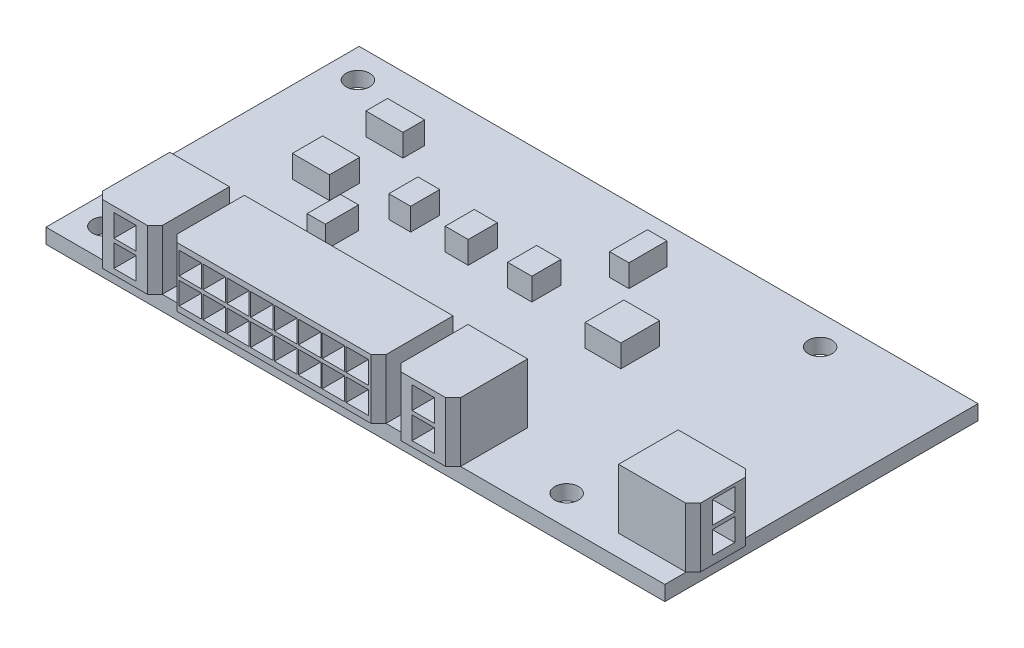
SolidWorks part; units mm, degrees
ref_plane "Front" through (0, 0, 0) normal (0, 0, 1) x (1, 0, 0)
ref_plane "Top" through (0, 0, 0) normal (0, 1, 0) x (1, 0, 0)
ref_plane "Right" through (0, 0, 0) normal (1, 0, 0) x (0, 0, -1)
sketch "Sketch1" plane through (0, 0, 0) normal (0, 1, 0) x (1, 0, 0)
  line L1 (0, 0) -> (83, 0)
  line L2 (0, 0) -> (0, 42)
  line L3 (0, 42) -> (83, 42)
  line L4 (83, 0) -> (83, 42)
  dimension "D1" = 42
  dimension "D2" = 83
extrude "Boss-Extrude1" add sketch "Sketch1" along normal blind 2
sketch "Sketch4" plane through (0, 2, 0) normal (0, 1, 0) x (1, 0, 0)
  line L0 (3.8264, 38) -> (65.8264, 38) construction
  line L1 (65.8264, 38) -> (65.8264, 4) construction
  line L2 (65.8264, 4) -> (3.8264, 4) construction
  line L3 (3.8264, 4) -> (3.8264, 38) construction
  line L4 (0, 0) -> (83, 0) construction
  line L5 (0, 42) -> (0, 0) construction
  circle A0 centre (3.8264, 38) radius 1.5875
  circle A1 centre (65.8264, 4) radius 1.5875
  circle A2 centre (3.8264, 4) radius 1.5875
  circle A3 centre (65.8264, 38) radius 1.5875
  dimension "D1" = 62
  dimension "D2" = 34
  dimension "D3" = 3.175
  dimension "D4" = 4
  dimension "D5" = 3.8264
extrude "Cut-Extrude2" cut sketch "Sketch4" against normal through all
sketch "Sketch5" plane through (0, 2, 0) normal (0, 1, 0) x (1, 0, 0)
  line L0 (17.6, 9) -> (45.6, 9)
  line L1 (7.6, 9) -> (15.6, 9)
  line L2 (7.6, 9) -> (7.6, 0)
  line L3 (8.6, -1) -> (14.6, -1)
  line L4 (15.6, 9) -> (15.6, 0)
  line L5 (17.6, 9) -> (17.6, 0)
  line L6 (45.6, 0) -> (44.6, -1)
  line L7 (18.6, -1) -> (44.6, -1)
  line L8 (45.6, 9) -> (45.6, 0)
  line L9 (47.6, 9) -> (55.6, 9)
  line L10 (47.6, 9) -> (47.6, 0)
  line L11 (48.6, -1) -> (54.6, -1)
  line L12 (55.6, 9) -> (55.6, 0)
  line L13 (55.6, 0) -> (54.6, -1)
  line L14 (7.6, 0) -> (8.6, -1)
  line L15 (15.6, 0) -> (14.6, -1)
  line L16 (17.6, 0) -> (18.6, -1)
  line L17 (47.6, 0) -> (48.6, -1)
  line L18 (73.9411, 2.8492) -> (73.9411, 10.8492)
  line L19 (73.9411, 2.8492) -> (82.9411, 2.8492)
  line L20 (83.9411, 3.8492) -> (83.9411, 9.8492)
  line L21 (73.9411, 10.8492) -> (82.9411, 10.8492)
  line L22 (82.9411, 10.8492) -> (83.9411, 9.8492)
  line L23 (82.9411, 2.8492) -> (83.9411, 3.8492)
extrude "Boss-Extrude2" add sketch "Sketch5" along normal blind 8
sketch "Sketch6" plane through (0, 0, 1) normal (0, 0, 1) x (1, 0, 0)
  line L0 (18.85, 5.75) -> (21.85, 5.75)
  line L1 (10.1, 9.25) -> (13.1, 9.25)
  line L2 (10.1, 9.25) -> (10.1, 6.25)
  line L3 (10.1, 6.25) -> (13.1, 6.25)
  line L4 (13.1, 9.25) -> (13.1, 6.25)
  line L5 (22.05, 5.75) -> (25.05, 5.75)
  line L6 (18.85, 2.75) -> (21.85, 2.75)
  line L7 (10.1, 5.75) -> (10.1, 2.75)
  line L8 (10.1, 5.75) -> (13.1, 5.75)
  line L9 (13.1, 5.75) -> (13.1, 2.75)
  line L10 (10.1, 2.75) -> (13.1, 2.75)
  line L11 (18.85, 9.25) -> (18.85, 6.25)
  line L12 (18.85, 5.75) -> (18.85, 2.75)
  line L13 (18.85, 9.25) -> (21.85, 9.25)
  line L14 (18.85, 6.25) -> (21.85, 6.25)
  line L15 (21.85, 5.75) -> (21.85, 2.75)
  line L16 (21.85, 9.25) -> (21.85, 6.25)
  line L17 (50.1, 9.25) -> (53.1, 9.25)
  line L18 (22.05, 2.75) -> (25.05, 2.75)
  line L19 (22.05, 9.25) -> (22.05, 6.25)
  line L20 (22.05, 5.75) -> (22.05, 2.75)
  line L21 (22.05, 9.25) -> (25.05, 9.25)
  line L22 (22.05, 6.25) -> (25.05, 6.25)
  line L23 (25.05, 5.75) -> (25.05, 2.75)
  line L24 (25.05, 9.25) -> (25.05, 6.25)
  line L25 (25.25, 5.75) -> (28.25, 5.75)
  line L26 (25.25, 2.75) -> (28.25, 2.75)
  line L27 (25.25, 9.25) -> (25.25, 6.25)
  line L28 (25.25, 5.75) -> (25.25, 2.75)
  line L29 (25.25, 9.25) -> (28.25, 9.25)
  line L30 (25.25, 6.25) -> (28.25, 6.25)
  line L31 (28.25, 5.75) -> (28.25, 2.75)
  line L32 (28.25, 9.25) -> (28.25, 6.25)
  line L33 (28.45, 5.75) -> (31.45, 5.75)
  line L34 (28.45, 2.75) -> (31.45, 2.75)
  line L35 (28.45, 9.25) -> (28.45, 6.25)
  line L36 (28.45, 5.75) -> (28.45, 2.75)
  line L37 (28.45, 9.25) -> (31.45, 9.25)
  line L38 (28.45, 6.25) -> (31.45, 6.25)
  line L39 (31.45, 5.75) -> (31.45, 2.75)
  line L40 (31.45, 9.25) -> (31.45, 6.25)
  line L41 (31.65, 5.75) -> (34.65, 5.75)
  line L42 (31.65, 2.75) -> (34.65, 2.75)
  line L43 (31.65, 9.25) -> (31.65, 6.25)
  line L44 (31.65, 5.75) -> (31.65, 2.75)
  line L45 (31.65, 9.25) -> (34.65, 9.25)
  line L46 (31.65, 6.25) -> (34.65, 6.25)
  line L47 (34.65, 5.75) -> (34.65, 2.75)
  line L48 (34.65, 9.25) -> (34.65, 6.25)
  line L49 (34.85, 5.75) -> (37.85, 5.75)
  line L50 (34.85, 2.75) -> (37.85, 2.75)
  line L51 (34.85, 9.25) -> (34.85, 6.25)
  line L52 (34.85, 5.75) -> (34.85, 2.75)
  line L53 (34.85, 9.25) -> (37.85, 9.25)
  line L54 (34.85, 6.25) -> (37.85, 6.25)
  line L55 (37.85, 5.75) -> (37.85, 2.75)
  line L56 (37.85, 9.25) -> (37.85, 6.25)
  line L57 (38.05, 5.75) -> (41.05, 5.75)
  line L58 (38.05, 2.75) -> (41.05, 2.75)
  line L59 (38.05, 9.25) -> (38.05, 6.25)
  line L60 (38.05, 5.75) -> (38.05, 2.75)
  line L61 (38.05, 9.25) -> (41.05, 9.25)
  line L62 (38.05, 6.25) -> (41.05, 6.25)
  line L63 (41.05, 5.75) -> (41.05, 2.75)
  line L64 (41.05, 9.25) -> (41.05, 6.25)
  line L65 (41.25, 5.75) -> (44.25, 5.75)
  line L66 (41.25, 2.75) -> (44.25, 2.75)
  line L67 (41.25, 9.25) -> (41.25, 6.25)
  line L68 (41.25, 5.75) -> (41.25, 2.75)
  line L69 (41.25, 9.25) -> (44.25, 9.25)
  line L70 (41.25, 6.25) -> (44.25, 6.25)
  line L71 (44.25, 5.75) -> (44.25, 2.75)
  line L72 (44.25, 9.25) -> (44.25, 6.25)
  line L74 (53.1, 9.25) -> (53.1, 6.25)
  line L75 (50.1, 2.75) -> (53.1, 2.75)
  line L76 (50.1, 5.75) -> (53.1, 5.75)
  line L77 (50.1, 9.25) -> (50.1, 6.25)
  line L78 (50.1, 6.25) -> (53.1, 6.25)
  line L79 (53.1, 5.75) -> (53.1, 2.75)
  line L80 (50.1, 5.75) -> (50.1, 2.75)
  dimension "D1" = 8
extrude "Cut-Extrude3" cut sketch "Sketch6" against normal blind 9
sketch "Sketch10" plane through (0, 2, 0) normal (0, 1, 0) x (1, 0, 0)
  line L1 (10.9532, 34.8514) -> (15.9259, 34.8514)
  line L2 (10.9532, 34.8514) -> (10.9532, 31.9506)
  line L3 (10.9532, 31.9506) -> (15.9259, 31.9506)
  line L4 (15.9259, 34.8514) -> (15.9259, 31.9506)
  line L5 (10.9532, 26.1537) -> (15.9259, 26.1537)
  line L6 (10.9532, 26.1537) -> (10.9532, 22.092)
  line L7 (10.9532, 22.092) -> (15.9259, 22.092)
  line L8 (15.9259, 26.1537) -> (15.9259, 22.092)
  line L9 (50.2132, 27.291) -> (55.0059, 27.291)
  line L10 (50.2132, 27.291) -> (50.2132, 22.092)
  line L11 (50.2132, 22.092) -> (55.0059, 22.092)
  line L12 (55.0059, 27.291) -> (55.0059, 22.092)
  line L13 (22.1064, 27.7784) -> (25.0308, 27.7784)
  line L14 (22.1064, 27.7784) -> (22.1064, 23.8792)
  line L15 (22.1064, 23.8792) -> (25.0308, 23.8792)
  line L16 (25.0308, 27.7784) -> (25.0308, 23.8792)
  line L17 (29.6611, 27.7784) -> (32.748, 27.7784)
  line L18 (29.6611, 27.7784) -> (29.6611, 23.8792)
  line L19 (29.6611, 23.8792) -> (32.748, 23.8792)
  line L20 (32.748, 27.7784) -> (32.748, 23.8792)
  line L21 (38.0281, 27.7784) -> (41.2775, 27.7784)
  line L22 (38.0281, 27.7784) -> (38.0281, 23.8792)
  line L23 (38.0281, 23.8792) -> (41.2775, 23.8792)
  line L24 (41.2775, 27.7784) -> (41.2775, 23.8792)
  line L25 (18.9383, 20.5486) -> (21.3753, 20.5486)
  line L26 (18.9383, 20.5486) -> (18.9383, 16.0808)
  line L27 (18.9383, 16.0808) -> (21.3753, 16.0808)
  line L28 (21.3753, 20.5486) -> (21.3753, 16.0808)
  line L29 (43.6333, 37.039) -> (46.2327, 37.039)
  line L30 (43.6333, 37.039) -> (43.6333, 31.9506)
  line L31 (43.6333, 31.9506) -> (46.2327, 31.9506)
  line L32 (46.2327, 37.039) -> (46.2327, 31.9506)
extrude "Boss-Extrude6" add sketch "Sketch10" along normal blind 3
sketch "Sketch11" plane through (83.9411, 0, 0) normal (1, 0, 0) x (0, 0, -1)
  line L0 (5.438, 9.6195) -> (8.438, 9.6195)
  line L1 (8.438, 9.6195) -> (8.438, 6.6195)
  line L2 (5.438, 3.1195) -> (8.438, 3.1195)
  line L3 (5.438, 6.1195) -> (8.438, 6.1195)
  line L4 (5.438, 9.6195) -> (5.438, 6.6195)
  line L5 (5.438, 6.6195) -> (8.438, 6.6195)
  line L6 (8.438, 6.1195) -> (8.438, 3.1195)
  line L7 (5.438, 6.1195) -> (5.438, 3.1195)
extrude "Cut-Extrude4" cut sketch "Sketch11" against normal blind 8
